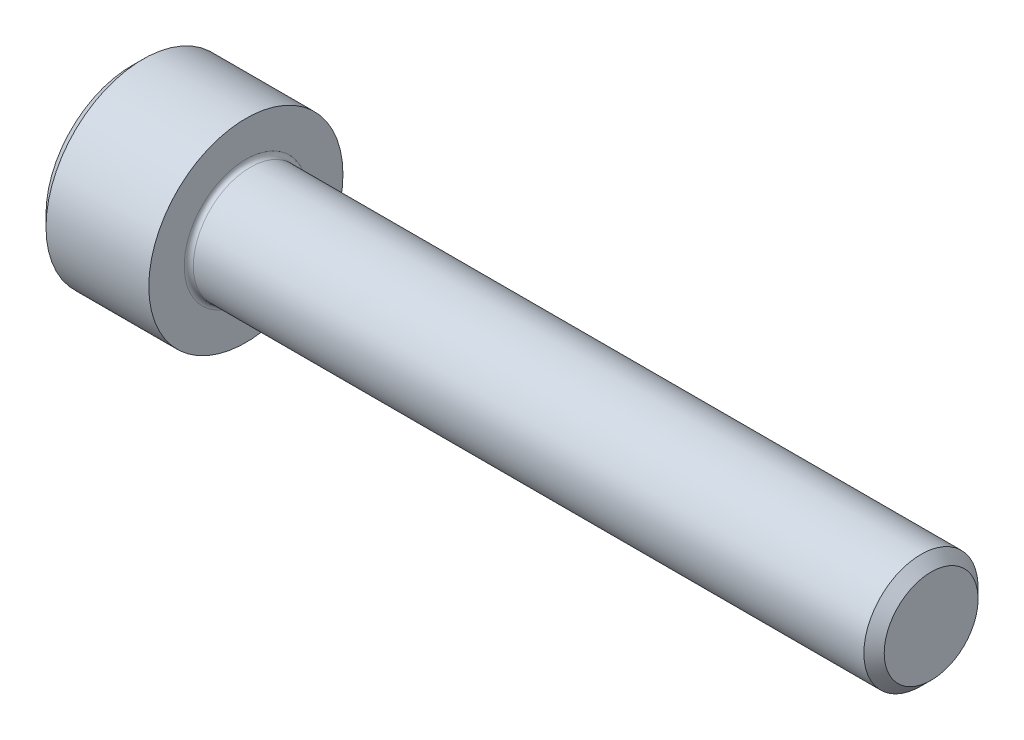
SolidWorks part; units mm, degrees
note: '?' marks a value the reader was unsure of.
revolve "Base-Revolve" add sketch "BodySke"
sketch "BodySke" plane through (0, 0, 0) normal (0, 0, 1) x (1, 0, 0)
  line L0 (0, 0) -> (0, 3.75)
  line L1 (0.5, 4.25) -> (5, 4.25)
  line L2 (5, 4.25) -> (5, 2.5)
  line L3 (5, 2.5) -> (34.555, 2.5)
  line L4 (35, 2.055) -> (35, 0)
  line L5 (35, 0) -> (0, 0)
  line L6 (-31.75, 0) -> (127, 0) construction
  line L7 (0, 3.75) -> (0.5, 4.25)
  line L8 (35, 2.055) -> (34.555, 2.5)
  line L9 (0, -3.75) -> (0.5, -4.25) construction
  line L10 (35, -2.055) -> (34.555, -2.5) construction
  line L11 (5.8, 9.525) -> (5.8, 3.175) construction
  line L12 (15, 9.525) -> (15, 3.175) construction
  line L13 (-15, 9.525) -> (-15, 3.175) construction
  dimension "Diameter" = 5
  dimension "Head_ht" = 5
  dimension "Length" = 30
  dimension "Body_ch_ang" = 45
  dimension "Head_dia" = 8.5
  dimension "Head_ch_ang" = 45
  dimension "Minor_dia" = 4.11
  dimension "Advance" = 0.8
  dimension "Thread_nom" = 20
  dimension "Thread_length" = 50
  dimension "Head_ch_ht" = 0.5
cosmetic thread "ThreadCosmetic" [suppressed]
fillet "Fillet1" radius 0.2 1 edges at (5, 0, 2.5)
ref_plane "Plane1" through (0, 0, 0) normal (0, 0, 1) x (1, 0, 0)
ref_plane "Plane2" through (0, 0, 0) normal (0, 1, 0) x (1, 0, 0)
ref_plane "Plane3" through (0, 0, 0) normal (1, 0, 0) x (0, 0, -1)
sketch "Sketch2" plane through (0, 0, 0) normal (0, 0, 1) x (1, 0, 0)
  line L0 (0, 2.042) -> (2.5, 2.042)
  line L1 (2.5, 2.042) -> (3.6789, 0)
  line L2 (-31.75, 0) -> (127, 0) construction
  line L3 (3.6789, 0) -> (0, 0)
  line L4 (0, 0) -> (0, 2.042)
  line L5 (0, 3.75) -> (0, -3.75) construction
  line L6 (0, 0) -> (47.625, 0) construction
  line L7 (5, -4.25) -> (5, 4.25) construction
  dimension "D1" = 2.042
  dimension "D2" = 60
revolve "Hex-PreBroach" [suppressed] cut sketch "Sketch2" angle 360 about L6
sketch "Sketch3" plane through (0, 0, 0) normal (-1, 0, 0) x (0, 0.5, 0.866)
  line L0 (1.1789, 2.042) -> (-1.1789, 2.042)
  line L1 (-1.1789, 2.042) -> (-2.3579, 0)
  line L2 (1.1789, 2.042) -> (2.3579, 0)
  line L3 (1.1789, -2.042) -> (2.3579, 0)
  line L4 (1.1789, -2.042) -> (-1.1789, -2.042)
  line L5 (-1.1789, -2.042) -> (-2.3579, 0)
  dimension "D1" = 2.042
  dimension "D2" = 2.042
extrude "Hex" [suppressed] cut sketch "Sketch3" against normal blind 2.5
sketch "Sketch4" plane through (0, 0, 0) normal (-1, 0, 0) x (0, 0, 1)
  line L0 (0, 0) -> (2.3876, 0)
  line L1 (0, 0) -> (6.1484, 3.5498) construction
  line L2 (0, 0) -> (1.1938, 2.0677)
  line L3 (1.9883, 0.576) -> (2.2704, 0.7389)
  line L4 (1.493, 1.4339) -> (1.7751, 1.5968)
  arc A0 (1.9883, 0.576) -> (1.493, 1.4339) centre (0, 0) ccw
  arc A1 (2.3876, 0) -> (2.2704, 0.7389) centre (0, 0) ccw
  arc A2 (1.1938, 2.0677) -> (1.7751, 1.5968) centre (0, 0) cw
  dimension "D1" = 30
  dimension "D2" = 60
  dimension "Spline_p_dim" = 0.9906
  dimension "D3" = 0.4953
extrude "Spline" [suppressed] cut sketch "Sketch4" against normal blind 2.5
pattern_circular "CirPattern1" [suppressed] count 0 every? 60?
sketch "Sketch5" plane through (0, 0, 0) normal (0, 0, 1) x (1, 0, 0)
  line L0 (-31.75, 0) -> (127, 0) construction
  line L2 (0, 3.75) -> (0, -3.75) construction
  circle A0 centre (2, 0) radius 0.675
  dimension "Drilled_hole_dia" = 1.35
  dimension "Drilled_hole_loc" = 2
extrude "Hole" [suppressed] cut sketch "Sketch5" against normal through all and the other way through all
pattern_circular "Drilled-4" [suppressed] count 2 every 60
pattern_circular "Drilled-6" [suppressed] count 3 every 60
sketch "ThdSchSke" plane through (0, 0, 0) normal (0, 0, 1) x (1, 0, 0)
  line L0 (5.8, -2.055) -> (5.4884, -2.5)
  line L1 (5.8, -2.055) -> (6.1116, -2.5)
  line L2 (6.1116, -2.5) -> (6.1116, -3.125)
  line L3 (-3.175, 0) -> (5.1513, 0) construction
  line L5 (6.1116, -3.125) -> (5.4884, -3.125)
  line L6 (5.4884, -3.125) -> (5.4884, -2.5)
  line L7 (0, 3.75) -> (0, -3.75) construction
  dimension "Thread_minor" = 4.11
  dimension "Diameter" = 5
revolve "ThreadSchematic" [suppressed] cut sketch "ThdSchSke" angle 360 about L3
pattern_linear "ThdSchPat" [suppressed]
equation "\"D2@Sketch3\" = \"Hex_size@Sketch3\" / 2"
equation "\"D1@Sketch3\" = \"Hex_size@Sketch3\" / 2"
equation "\"D1@Sketch2\" = \"Hex_size@Sketch3\" / 2"
equation "\"D3@Sketch4\" = \"Spline_p_dim@Sketch4\" / 2"
equation "\"Thread_minor@ThreadCosmetic\"  =  \"Minor_dia@BodySke\""
equation "\"D2@CirPattern1\" = 360 / \"Num_teeth@CirPattern1\""
equation "\"Wall_thickness@Sketch2\" = \"Head_ht@BodySke\" - \"Key_eng@Hex\""
equation "\"Thread_length@ThreadCosmetic\" = ((sgn( (\"Length@BodySke\" - \"Advance@BodySke\" ) - \"Thread_nom@BodySke\" )-1)*( (\"Length@BodySke\" - \"Advance@BodySke\" ) - \"Thread_nom@BodySke\" ))/-2+ \"Thread_nom@BodySke\""
equation "\"Thread_minor@ThdSchSke\" = \"Minor_dia@BodySke\""
equation "\"Diameter@ThdSchSke\" = \"Diameter@BodySke\""
equation "\"Overcut@ThdSchSke\" = \"Diameter@BodySke\" * 1.25"
equation "\"Start@ThdSchSke\" = \"Head_ht@BodySke\" + \"Length@BodySke\" - \"Thread_length@ThreadCosmetic\"  '---Non-countersunk---"
equation "\"Num_threads@ThdSchPat\" = int( \"Thread_length@ThreadCosmetic\" / \"Advance@BodySke\" + 0.999 )  + 1"
equation "\"Advance@ThdSchPat\" = \"Thread_length@ThreadCosmetic\" /  (\"Num_threads@ThdSchPat\" - 1) 'relax it"
equation "\"Num_threads@ThdSchPat\" = \"Num_threads@ThdSchPat\" - sgn( \"Num_threads@ThdSchPat\" - 1) '---chamfered tips only---"
